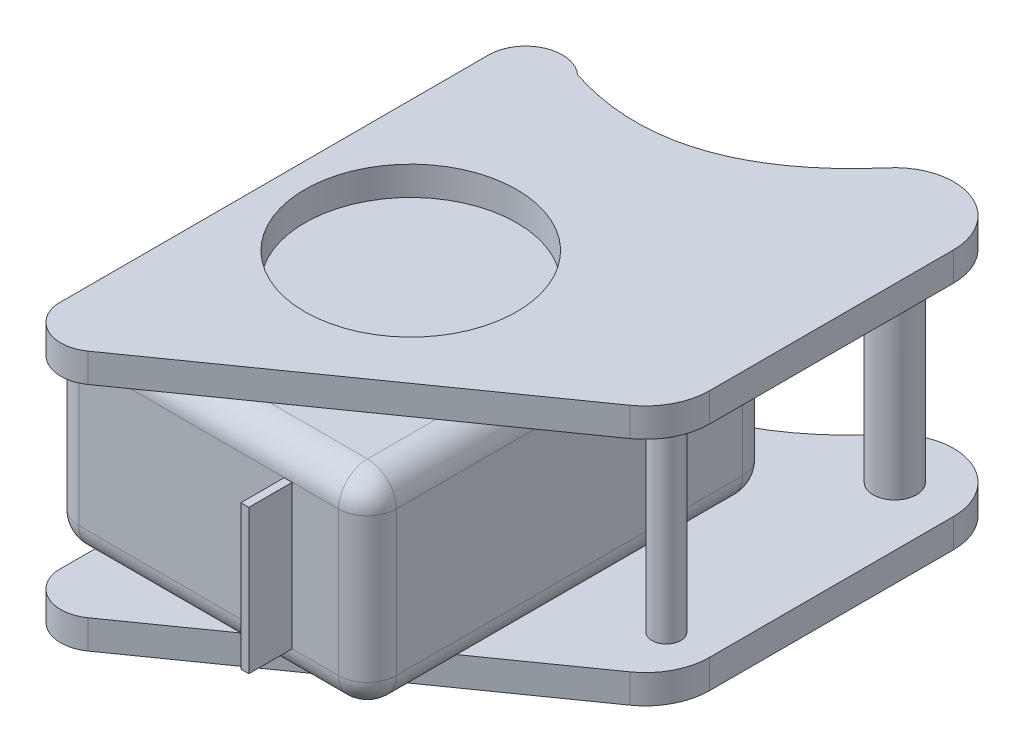
SolidWorks part; units mm, degrees
note: The reader was unsure of these and kept them because the rebuilt part matched: shared geometry of "Sketch4<2>".
ref_plane "Front Plane" through (0, 0, 0) normal (0, 0, 1) x (1, 0, 0)
ref_plane "Top Plane" through (0, 0, 0) normal (0, 1, 0) x (1, 0, 0)
ref_plane "Right Plane" through (0, 0, 0) normal (1, 0, 0) x (0, 0, -1)
sketch "Sketch1" plane through (0, 0, 0) normal (0, 0, 1) x (1, 0, 0)
  line L1 (-11, -7) -> (11, -7)
  line L2 (-11, -7) -> (-11, 7)
  line L3 (-11, 7) -> (11, 7)
  line L4 (11, -7) -> (11, 7)
  line L5 (-11, -7) -> (11, 7) construction
  line L6 (-11, 7) -> (11, -7) construction
  point P0 (0, 0)
  dimension "D1" = 14
  dimension "D2" = 22
extrude "Boss-Extrude1" add sketch "Sketch1" along normal mid plane 28
fillet "Fillet1" radius 2 12 edges at (0, 7, -14) (-11, 7, 0) (-11, 0, -14) (-11, 0, 14) (0, 7, 14) (-11, -7, 0) (0, -7, 14) (0, -7, -14) (11, -7, 0) (11, 0, 14) (11, 7, 0) (11, 0, -14)
sketch "Sketch2" plane through (-11, 0, 0) normal (-1, 0, 0) x (0, 0, 1)
  line L0 (12, -5) -> (12, 5) construction
  circle A0 centre (-10.5654, 3.6892) radius 1
  circle A1 centre (10.5, 3.6892) radius 1
  circle A2 centre (10.5, -3.4272) radius 1
  circle A3 centre (-10.5654, -3.4272) radius 1
  dimension "D1" = 2
  dimension "D2" = 2
  dimension "D3" = 2
  dimension "D4" = 2
  dimension "D5" = 1.5
  dimension "D6" = 0
extrude "Cut-Extrude1" cut sketch "Sketch2" against normal blind 19
sketch "Sketch3" plane through (0, 0, -14) normal (0, 0, -1) x (-1, 0, 0)
  line L0 (-9, -5) -> (9, -5) construction
  line L1 (-5.7813, 4.9867) -> (-5.2268, 4.9867)
  line L2 (-5.7813, 4.9867) -> (-5.7813, -5)
  line L3 (-5.7813, -5) -> (-5.2268, -5)
  line L4 (-5.2268, 4.9867) -> (-5.2268, -5)
  line L5 (-5.7813, 4.9867) -> (-5.2268, -5) construction
  line L6 (-5.7813, -5) -> (-5.2268, 4.9867) construction
  point P0 (-5.504, -0.0067)
extrude "Boss-Extrude2" add sketch "Sketch3" along normal blind 3 and the other way offset from surface (31 mm away) 3 other way up to face at (0, 0, 14)
sketch "Sketch4" plane through (-11, 0, 0) normal (-1, 0, 0) x (0, 0, 1)
  circle A0 centre (5.4165, 0) radius 1.5
  circle A1 centre (5.4165, 0) radius 2
  dimension "D1" = 3
  dimension "D2" = 4
extrude "Boss-Extrude3" add sketch "Sketch4" along normal blind 0.8
extrude "Cut-Extrude2" cut sketch "Sketch4<2>" against normal blind 10 contours A0
sketch "Sketch4<2>" plane through (-11, 0, 0) normal (-1, 0, 0) x (0, 0, 1) same geometry as "Sketch4"
sketch "Sketch5" plane through (0, -7, 0) normal (0, -1, 0) x (1, 0, 0)
  line L0 (-5.1553, 17.2129) -> (16.8705, 1.6829)
  line L2 (-9.0444, 15.5053) -> (-9.0444, -14.4498)
  line L4 (18.7581, -1.9574) -> (18.7581, -18.8627)
  arc A0 (11.5081, -21.436) -> (18.7581, -18.8627) centre (14.6764, -18.8627) ccw
  arc A1 (18.7581, -1.9574) -> (16.8705, 1.6829) centre (14.3038, -1.9574) ccw
  arc A2 (-5.1553, 17.2129) -> (-9.0444, 14.866) centre (-6.5846, 15.1857) ccw
  arc A3 (-9.0444, -14.4498) -> (-4.7845, -16.3429) centre (-6.4938, -14.4498) ccw
  circle A4 centre (0, 0) radius 7.186
  spline S0 degree 3 poles (-4.7845, -16.3429) (1.3406, -14.3061) (6.7715, -16.0038) (11.5081, -21.436) knots 0.0843 0.0843 0.0843 0.0843 1 1 1 1
  line M1 (9, 12) -> (-9, 12)
  line M2 (-9, 12) -> (-9, -12)
  line M3 (-9, -12) -> (9, -12)
  line M4 (9, -12) -> (9, 12)
extrude "Boss-Extrude5" add sketch "Sketch5" along normal blind 2 contours A3 S0 A0 L4 A1 L0 A2 L2 M4 M3 M2 M1 | L0 A4 M1 M2 M3 M4
sketch "Sketch6" plane through (0, 7, 0) normal (0, 1, 0) x (1, 0, 0)
  line L3 (-5.1553, -17.2129) -> (16.8705, -1.6829)
  line L4 (9, -12) -> (9, 12)
  line L5 (9, 12) -> (-9, 12)
  line L6 (-9, 12) -> (-9, -12)
  line L7 (-9, -12) -> (9, -12)
  line L10 (-9, 12) -> (-9, -12)
  line L12 (-9.0444, 14.4498) -> (-9.0444, -15.5053)
  line L13 (18.7581, 1.9574) -> (18.7581, 18.8627)
  line L14 (-5.1553, -17.2129) -> (16.8705, -1.6829)
  line L15 (-9.0444, 14.4498) -> (-9.0444, -15.5053)
  line L16 (18.7581, 1.9574) -> (18.7581, 18.8627)
  circle A0 centre (0, 0) radius 7.3417
  arc A4 (-9.0444, -15.5053) -> (-5.1553, -17.2129) centre (-6.5846, -15.1857) ccw
  arc A5 (-4.7845, 16.3429) -> (-9.0444, 14.4498) centre (-6.4938, 14.4498) ccw
  arc A6 (18.7581, 18.8627) -> (11.5081, 21.436) centre (14.6764, 18.8627) ccw
  arc A7 (16.8705, -1.6829) -> (18.7581, 1.9574) centre (14.3038, 1.9574) ccw
  arc A8 (-9.0444, -15.5053) -> (-5.1553, -17.2129) centre (-6.5846, -15.1857) ccw
  arc A9 (-4.7845, 16.3429) -> (-9.0444, 14.4498) centre (-6.4938, 14.4498) ccw
  arc A10 (18.7581, 18.8627) -> (11.5081, 21.436) centre (14.6764, 18.8627) ccw
  arc A11 (16.8705, -1.6829) -> (18.7581, 1.9574) centre (14.3038, 1.9574) ccw
  parabola Q1 (11.5081, 21.436) -> (-4.7845, 16.3429) focus (1.2632, 21.92) apex (2.415, 15.7239)
  parabola Q2 (11.5081, 21.436) -> (-4.7845, 16.3429) focus (1.2632, 21.92) apex (2.415, 15.7239)
  line M13 (9, -12) -> (9, 12)
  line M14 (9, 12) -> (-9, 12)
  line M15 (-9, 12) -> (-9, -12)
  line M16 (-9, -12) -> (9, -12)
  dimension "D1" = 0
  dimension "D2" = 0
extrude "Boss-Extrude6" add sketch "Sketch6" along normal blind 2 contours A10 Q2 A9 L15 A8 L14 A11 L16 M16 M15 M14 M13 | L14 A0 M16 M13 M14 M15
sketch "Sketch7" plane through (0, -7, 0) normal (0, 1, 0) x (1, 0, 0)
  circle A0 centre (14.6764, 18.8627) radius 1.5
  arc A1 (18.7581, 18.8627) -> (11.5081, 21.436) centre (14.6764, 18.8627) ccw construction
  dimension "D1" = 3
extrude "Boss-Extrude7" add sketch "Sketch7" along normal up to surface (14 mm away) up to face at (3.7312, 7, -2.8137)
sketch "Sketch8" plane through (0, 7, 0) normal (0, -1, 0) x (1, 0, 0)
  line L1 (18.7581, -1.9574) -> (18.7581, -18.8627) construction
  circle A0 centre (15.7581, -1.9574) radius 1
  dimension "D1" = 2
  dimension "D2" = 3
extrude "Boss-Extrude8" add sketch "Sketch8" along normal up to surface (14 mm away) up to face at (2.4779, -7, -2.4219)
